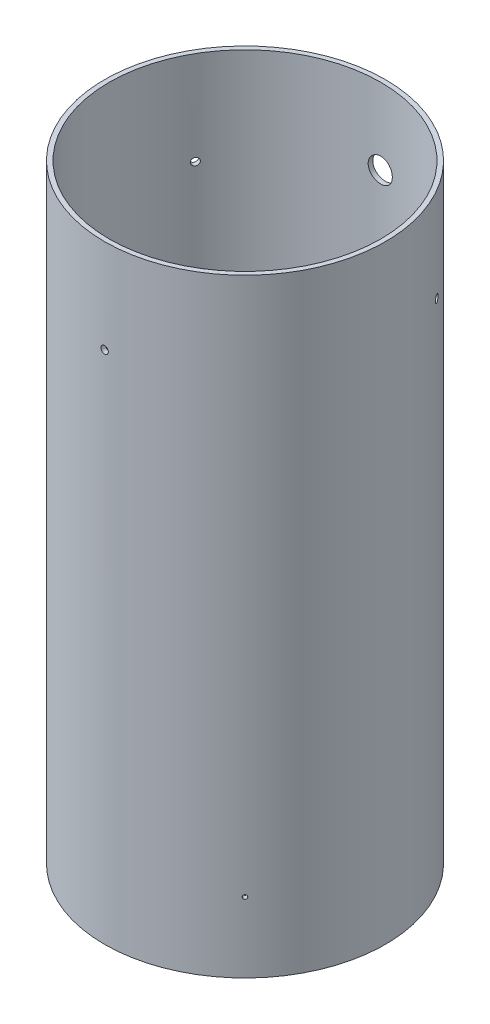
SolidWorks part; units mm, degrees
material "A-Glass Fiber"
ref_plane "Front Plane" through (0, 0, 0) normal (0, 0, 1) x (1, 0, 0)
ref_plane "Top Plane" through (0, 0, 0) normal (0, 1, 0) x (1, 0, 0)
ref_plane "Right Plane" through (0, 0, 0) normal (1, 0, 0) x (0, 0, -1)
sketch "Sketch1" plane through (0, 0, 0) normal (0, 1, 0) x (1, 0, 0)
  circle A0 centre (0, 0) radius 76.1746
  circle A1 centre (0, 0) radius 73.66
  dimension "D1" = 152.3492
  dimension "D2" = 147.32
extrude "Boss-Extrude1" add sketch "Sketch1" along normal blind 330.2
sketch "Sketch4" plane through (0, 0, 0) normal (0, 0, 1) x (1, 0, 0)
  line L0 (-76.1746, 0) -> (76.1746, 0) construction
  line L1 (76.1746, 330.2) -> (-76.1746, 330.2) construction
  line L2 (0, 330.2) -> (0, 0) construction
  line L3 (73.66, 330.2) -> (-73.66, 330.2) construction
  point P0 (0, 41.275)
  point P3 (0, 288.925)
  dimension "D1" = 41.275
  dimension "D2" = 41.275
hole_wizard "1/2 Clearance Hole5" positions "Sketch16" profile "Sketch17" hole size "1/2" standard "ANSI Inch"
sketch "Sketch16" plane through (0, 0, 0) normal (0, 0, 1) x (1, 0, 0)
  point P0 (0, 288.925)
sketch "Sketch17" plane through (0, 288.925, 0) normal (1, 0, 0) x (0, -1, 0)
  line L0 (0, 0) -> (0, 80.1345)
  line L1 (0, 80.1345) -> (6.5481, 76.2)
  line L2 (6.5481, 76.2) -> (6.5481, 0)
  line L5 (6.5481, 0) -> (0, 0)
  line L10 (0, 80.1345) -> (-6.5481, 76.2) construction
  line L11 (0, -6.35) -> (0, 107.95) construction
  dimension "Hole Dia." = 13.0962
  dimension "Hole Depth" = 76.2
  dimension "Drill Angle" = 118
hole_wizard "1/2 Clearance Hole7" positions "Sketch20" profile "Sketch21" hole size "1/2" standard "ANSI Inch"
sketch "Sketch20" plane through (0, 0, 0) normal (0, 0, 1) x (1, 0, 0)
  point P0 (0, 41.275)
sketch "Sketch21" plane through (0, 41.275, 0) normal (1, 0, 0) x (0, -1, 0)
  line L0 (0, 0) -> (0, 80.1345)
  line L1 (0, 80.1345) -> (6.5481, 76.2)
  line L2 (6.5481, 76.2) -> (6.5481, 0)
  line L5 (6.5481, 0) -> (0, 0)
  line L10 (0, 80.1345) -> (-6.5481, 76.2) construction
  line L11 (0, -6.35) -> (0, 107.95) construction
  dimension "Hole Dia." = 13.0962
  dimension "Hole Depth" = 76.2
  dimension "Drill Angle" = 118
ref_plane "Plane1" through (0, 0, 0) normal (-0.7071, 0, 0.7071) x (0.7071, 0, 0.7071)
sketch "Sketch23" plane through (0, 0, 0) normal (-0.7071, 0, 0.7071) x (0.7071, 0, 0.7071)
  line L0 (0, 0) -> (0, 330.2) construction
  line L1 (73.66, 330.2) -> (-73.66, 330.2) construction
  line L2 (-76.1746, 165.1) -> (76.1746, 165.1) construction
  line L3 (76.1746, 0) -> (76.1746, 330.2) construction
  circle A1 centre (0, 38.1) radius 1.0922
  point P12 (0, 165.1)
  dimension "D2" = 127
extrude "Shear Scrrews" cut sketch "Sketch23" against normal through all
pattern_circular "CirPattern1" count 4 over 360 about axis through (0, 330.2, 0) along (0, -1, 0) of "Shear Scrrews"
hole_wizard "Ø4.0 (4) Diameter Hole1" positions "Sketch24" profile "Sketch25" hole size "Ø4.0" standard "ANSI Metric"
sketch "Sketch24" plane through (0, 0, 0) normal (0, 0, 1) x (1, 0, 0)
  line L0 (76.1746, 330.2) -> (-76.1746, 330.2) construction
  point P0 (0, 279.4)
  dimension "D1" = 50.8
sketch "Sketch25" plane through (0, 279.4, 0) normal (1, 0, 0) x (0, 1, 0)
  line L0 (0, 0) -> (0, 90.1017)
  line L1 (0, 90.1017) -> (2, 88.9)
  line L2 (2, 88.9) -> (2, 0)
  line L5 (2, 0) -> (0, 0)
  line L10 (0, 90.1017) -> (-2, 88.9) construction
  line L11 (0, -6.35) -> (0, 107.95) construction
  dimension "Hole Dia." = 4
  dimension "Hole Depth" = 88.9
  dimension "Drill Angle" = 118
pattern_circular "CirPattern2" count 3 over 360 about axis through (0, 330.2, 0) along (0, 1, 0) of "Ø4.0 (4) Diameter Hole1"
equation "\"Mid_Coupler_Length\" = 13in"
equation "\"D1@Boss-Extrude1\"=\"Mid_Coupler_Length\""
equation "\"Shear_Screw_Coupler_Location\" = 4.5in"
equation "\"Shear_Screw_Diameter\" = 0.086in"
equation "\"D2@Sketch23\"=\"Shear_Screw_Coupler_Location\"+0.5"
